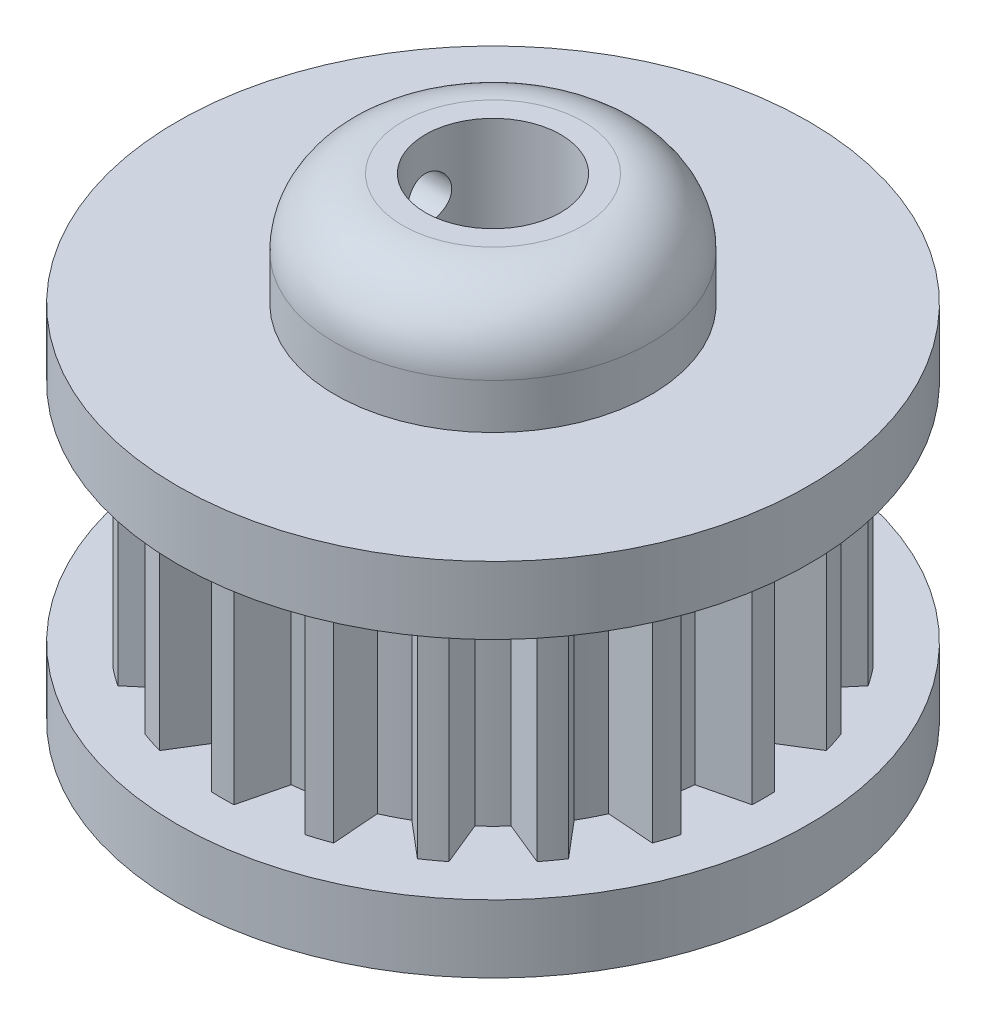
SolidWorks part; units mm, degrees
ref_plane "Front Plane" through (0, 0, 0) normal (0, 0, 1) x (1, 0, 0)
ref_plane "Top Plane" through (0, 0, 0) normal (0, 1, 0) x (1, 0, 0)
ref_plane "Right Plane" through (0, 0, 0) normal (1, 0, 0) x (0, 0, -1)
sketch "Sketch3" plane through (0, 0, 0) normal (0, 1, 0) x (1, 0, 0)
  line L0 (0, 12) -> (0, 10) construction
  line L1 (1, 9.9499) -> (0.5, 11.9896)
  line L2 (-1, 9.9499) -> (-0.5, 11.9896)
  line L3 (4.0257, 9.1539) -> (4.1805, 11.2483)
  line L4 (2.1236, 9.7719) -> (3.2295, 11.5573)
  line L5 (6.6574, 7.4618) -> (7.4518, 9.4059)
  line L6 (5.0394, 8.6374) -> (6.6428, 9.9937)
  line L7 (8.6374, 5.0394) -> (9.9937, 6.6428)
  line L8 (7.4618, 6.6574) -> (9.4059, 7.4518)
  line L9 (9.7719, 2.1236) -> (11.5573, 3.2295)
  line L10 (9.1539, 4.0257) -> (11.2483, 4.1805)
  line L11 (9.9499, -1) -> (11.9896, -0.5)
  line L12 (9.9499, 1) -> (11.9896, 0.5)
  line L13 (9.1539, -4.0257) -> (11.2483, -4.1805)
  line L14 (9.7719, -2.1236) -> (11.5573, -3.2295)
  line L15 (7.4618, -6.6574) -> (9.4059, -7.4518)
  line L16 (8.6374, -5.0394) -> (9.9937, -6.6428)
  line L17 (5.0394, -8.6374) -> (6.6428, -9.9937)
  line L18 (6.6574, -7.4618) -> (7.4518, -9.4059)
  line L19 (2.1236, -9.7719) -> (3.2295, -11.5573)
  line L20 (4.0257, -9.1539) -> (4.1805, -11.2483)
  line L21 (-1, -9.9499) -> (-0.5, -11.9896)
  line L22 (1, -9.9499) -> (0.5, -11.9896)
  line L23 (-4.0257, -9.1539) -> (-4.1805, -11.2483)
  line L24 (-2.1236, -9.7719) -> (-3.2295, -11.5573)
  line L25 (-6.6574, -7.4618) -> (-7.4518, -9.4059)
  line L26 (-5.0394, -8.6374) -> (-6.6428, -9.9937)
  line L27 (-8.6374, -5.0394) -> (-9.9937, -6.6428)
  line L28 (-7.4618, -6.6574) -> (-9.4059, -7.4518)
  line L29 (-9.7719, -2.1236) -> (-11.5573, -3.2295)
  line L30 (-9.1539, -4.0257) -> (-11.2483, -4.1805)
  line L31 (-9.9499, 1) -> (-11.9896, 0.5)
  line L32 (-9.9499, -1) -> (-11.9896, -0.5)
  line L33 (-9.1539, 4.0257) -> (-11.2483, 4.1805)
  line L34 (-9.7719, 2.1236) -> (-11.5573, 3.2295)
  line L35 (-7.4618, 6.6574) -> (-9.4059, 7.4518)
  line L36 (-8.6374, 5.0394) -> (-9.9937, 6.6428)
  line L37 (-5.0394, 8.6374) -> (-6.6428, 9.9937)
  line L38 (-6.6574, 7.4618) -> (-7.4518, 9.4059)
  line L39 (-2.1236, 9.7719) -> (-3.2295, 11.5573)
  line L40 (-4.0257, 9.1539) -> (-4.1805, 11.2483)
  circle A0 centre (0, 0) radius 3
  circle A1 centre (0, 0) radius 12 construction
  arc A2 (-1, 9.9499) -> (-2.1236, 9.7719) centre (0, 0) ccw
  arc A3 (0.5, 11.9896) -> (-0.5, 11.9896) centre (0, 0) ccw
  arc A4 (4.1805, 11.2483) -> (3.2295, 11.5573) centre (0, 0) ccw
  arc A5 (7.4518, 9.4059) -> (6.6428, 9.9937) centre (0, 0) ccw
  arc A6 (9.9937, 6.6428) -> (9.4059, 7.4518) centre (0, 0) ccw
  arc A7 (11.5573, 3.2295) -> (11.2483, 4.1805) centre (0, 0) ccw
  arc A8 (11.9896, -0.5) -> (11.9896, 0.5) centre (0, 0) ccw
  arc A9 (11.2483, -4.1805) -> (11.5573, -3.2295) centre (0, 0) ccw
  arc A10 (9.4059, -7.4518) -> (9.9937, -6.6428) centre (0, 0) ccw
  arc A11 (6.6428, -9.9937) -> (7.4518, -9.4059) centre (0, 0) ccw
  arc A12 (3.2295, -11.5573) -> (4.1805, -11.2483) centre (0, 0) ccw
  arc A13 (-0.5, -11.9896) -> (0.5, -11.9896) centre (0, 0) ccw
  arc A14 (-4.1805, -11.2483) -> (-3.2295, -11.5573) centre (0, 0) ccw
  arc A15 (-7.4518, -9.4059) -> (-6.6428, -9.9937) centre (0, 0) ccw
  arc A16 (-9.9937, -6.6428) -> (-9.4059, -7.4518) centre (0, 0) ccw
  arc A17 (-11.5573, -3.2295) -> (-11.2483, -4.1805) centre (0, 0) ccw
  arc A18 (-11.9896, 0.5) -> (-11.9896, -0.5) centre (0, 0) ccw
  arc A19 (-11.2483, 4.1805) -> (-11.5573, 3.2295) centre (0, 0) ccw
  arc A20 (-9.4059, 7.4518) -> (-9.9937, 6.6428) centre (0, 0) ccw
  arc A21 (-6.6428, 9.9937) -> (-7.4518, 9.4059) centre (0, 0) ccw
  arc A22 (-3.2295, 11.5573) -> (-4.1805, 11.2483) centre (0, 0) ccw
  arc A23 (-4.0257, 9.1539) -> (-5.0394, 8.6374) centre (0, 0) ccw
  arc A24 (-6.6574, 7.4618) -> (-7.4618, 6.6574) centre (0, 0) ccw
  arc A25 (-8.6374, 5.0394) -> (-9.1539, 4.0257) centre (0, 0) ccw
  arc A26 (-9.7719, 2.1236) -> (-9.9499, 1) centre (0, 0) ccw
  arc A27 (-9.9499, -1) -> (-9.7719, -2.1236) centre (0, 0) ccw
  arc A28 (-9.1539, -4.0257) -> (-8.6374, -5.0394) centre (0, 0) ccw
  arc A29 (2.1236, 9.7719) -> (1, 9.9499) centre (0, 0) ccw
  arc A30 (5.0394, 8.6374) -> (4.0257, 9.1539) centre (0, 0) ccw
  arc A31 (7.4618, 6.6574) -> (6.6574, 7.4618) centre (0, 0) ccw
  arc A32 (9.1539, 4.0257) -> (8.6374, 5.0394) centre (0, 0) ccw
  arc A33 (9.9499, 1) -> (9.7719, 2.1236) centre (0, 0) ccw
  arc A34 (9.7719, -2.1236) -> (9.9499, -1) centre (0, 0) ccw
  arc A35 (8.6374, -5.0394) -> (9.1539, -4.0257) centre (0, 0) ccw
  arc A36 (6.6574, -7.4618) -> (7.4618, -6.6574) centre (0, 0) ccw
  arc A37 (4.0257, -9.1539) -> (5.0394, -8.6374) centre (0, 0) ccw
  arc A38 (1, -9.9499) -> (2.1236, -9.7719) centre (0, 0) ccw
  arc A39 (-2.1236, -9.7719) -> (-1, -9.9499) centre (0, 0) ccw
  arc A40 (-5.0394, -8.6374) -> (-4.0257, -9.1539) centre (0, 0) ccw
  arc A41 (-7.4618, -6.6574) -> (-6.6574, -7.4618) centre (0, 0) ccw
  point P90 (0, 0)
  dimension "D1" = 24
  dimension "D2" = 6
  dimension "D3" = 20
  dimension "D4" = 1
  dimension "D5" = 0.5
  dimension "D6" = 20
extrude "Boss-Extrude2" add sketch "Sketch3" along normal blind 10
sketch "Sketch4" plane through (0, 0, 0) normal (1, 0, 0) x (0, 0, -1)
  line L0 (0, -1000) -> (0, 49000) construction
  line L1 (0, 10) -> (14, 10)
  line L2 (0.5, 10) -> (-0.5, 10) construction
  line L3 (14, 10) -> (14, 13)
  line L4 (14, 13) -> (7, 13)
  line L5 (7, 13) -> (7, 18)
  line L6 (7, 18) -> (0, 18)
  line L7 (0, 18) -> (0, 10)
  line L8 (-1011.9896, 5) -> (48988.0104, 5) construction
  line L9 (-11.9896, 10) -> (-11.9896, 0) construction
  line L10 (7, -8) -> (0, -8)
  line L11 (7, -3) -> (7, -8)
  line L12 (14, -3) -> (7, -3)
  line L13 (14, 0) -> (14, -3)
  line L14 (0, 0) -> (14, 0)
  line L15 (0, -8) -> (0, 0)
  point P16 (-11.9896, 5)
  dimension "D1" = 14
  dimension "D2" = 7
  dimension "D3" = 8
  dimension "3" = 3
revolve "Revolve1" add sketch "Sketch4" angle 360 about L0 region at (0, -3.3182, -5.4091)
sketch "Sketch5" plane through (0, -8, 0) normal (0, -1, 0) x (1, 0, 0)
  circle A0 centre (0, 0) radius 3
  dimension "D1" = 6
extrude "Cut-Extrude1" cut sketch "Sketch5" against normal blind 27
sketch "Sketch6" plane through (0, 0, 0) normal (1, 0, 0) x (0, 0, -1)
  line L0 (0, 18) -> (0, 13) construction
  line L1 (7, 18) -> (-7, 18) construction
  line L2 (14, 13) -> (-14, 13) construction
  line L3 (-11.9896, 5) -> (11.9896, 5) construction
  line L4 (-11.9896, 10) -> (-11.9896, 0) construction
  line L5 (11.9896, 10) -> (11.9896, 0) construction
  circle A0 centre (0, 15.5) radius 1
  circle A1 centre (0, -5.5) radius 1
  dimension "D1" = 2
extrude "Cut-Extrude2" cut sketch "Sketch6" against normal blind 8
fillet "Fillet1" radius 3 2 edges at (0, -8, -7) (0, 18, -7)
